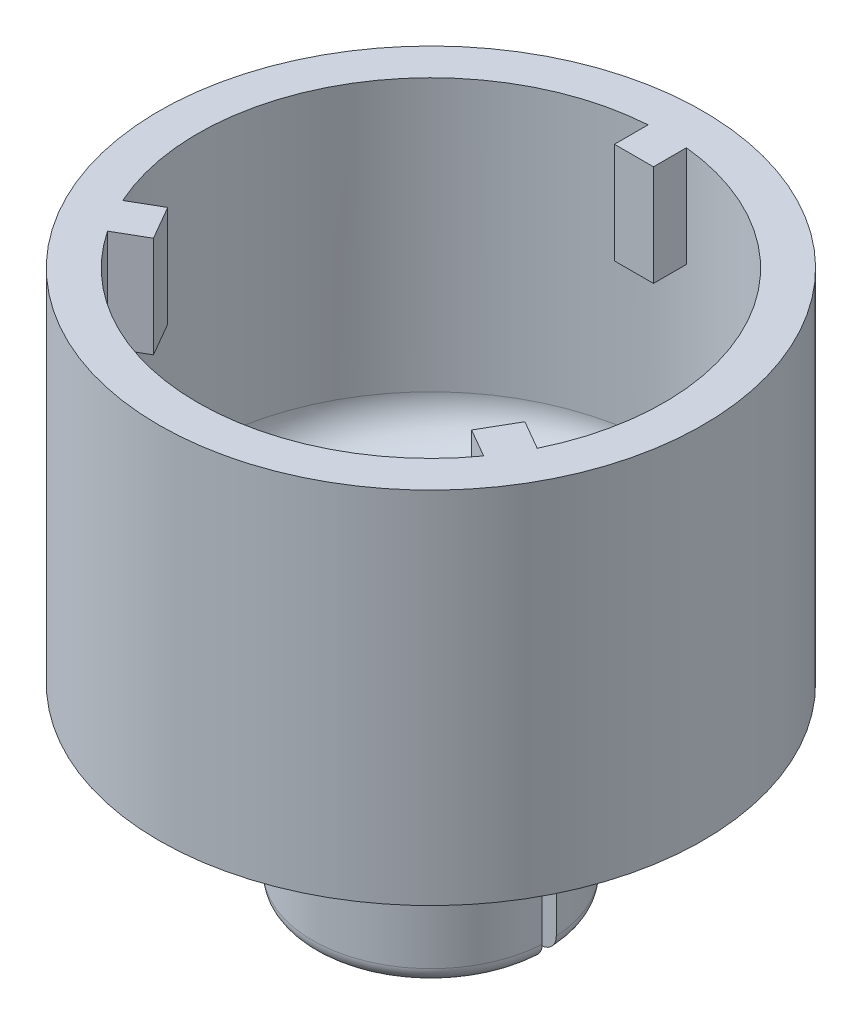
SolidWorks part; units mm, degrees
ref_plane "Front Plane" through (0, 0, 0) normal (0, 0, 1) x (1, 0, 0)
ref_plane "Top Plane" through (0, 0, 0) normal (0, 1, 0) x (1, 0, 0)
ref_plane "Right Plane" through (0, 0, 0) normal (1, 0, 0) x (0, 0, -1)
sketch "Sketch1" plane through (0, 0, 0) normal (0, 1, 0) x (1, 0, 0)
  circle A0 centre (0, 0) radius 35
  dimension "D1" = 70
extrude "Boss-Extrude1" add sketch "Sketch1" along normal blind 46.3
sketch "Sketch2" plane through (0, 46.3, 0) normal (0, 1, 0) x (1, 0, 0)
  circle A0 centre (0, 0) radius 30
  dimension "D1" = 60
extrude "Cut-Extrude1" cut sketch "Sketch2" against normal blind 40
sketch "Sketch3" plane through (0, 0, 0) normal (0, -1, 0) x (1, 0, 0)
  circle A0 centre (0, 0) radius 19.5
  dimension "D1" = 39
extrude "Boss-Extrude2" add sketch "Sketch3" along normal blind 7
sketch "Sketch4" plane through (0, -7, 0) normal (0, -1, 0) x (1, 0, 0)
  circle A0 centre (0, 0) radius 15.25
  dimension "D1" = 30.5
extrude "Boss-Extrude3" add sketch "Sketch4" along normal blind 16
fillet "Fillet1" radius 5 1 edges at (0, 0, -19.5)
sketch "Sketch5" plane through (0, 46.3, 0) normal (0, 1, 0) x (1, 0, 0)
  line L0 (-1.9905, 29.9339) -> (-1.9905, 25.6053)
  line L1 (-1.9905, 25.6053) -> (3.0302, 25.6053)
  line L2 (3.0302, 25.6053) -> (3.0302, 29.8466)
  line L3 (26.9188, -13.2431) -> (23.1701, -11.0788)
  line L4 (23.1701, -11.0788) -> (20.6597, -15.4269)
  line L5 (20.6597, -15.4269) -> (24.3328, -17.5475)
  line L6 (-24.9282, -16.6908) -> (-21.1796, -14.5265)
  line L7 (-21.1796, -14.5265) -> (-23.69, -10.1784)
  line L8 (-23.69, -10.1784) -> (-27.363, -12.299)
  circle A0 centre (0, 0) radius 30 construction
  arc A1 (24.3328, -17.5475) -> (26.9188, -13.2431) centre (0, 0) ccw
  circle A2 centre (0, 0) radius 30
  arc A3 (3.0302, 29.8466) -> (-1.9905, 29.9339) centre (0, 0) ccw
  arc A4 (-27.363, -12.299) -> (-24.9282, -16.6908) centre (0, 0) ccw
  point P19 (0, 0)
  dimension "D1" = 0
  dimension "D2" = 3
extrude "Boss-Extrude4" add sketch "Sketch5" against normal blind 13
sketch "Sketch7" plane through (0, -23, 0) normal (0, -1, 0) x (1, 0, 0)
  line L1 (33.0968, 0.9034) -> (-33.0968, 0.9034)
  line L2 (33.0968, 0.9034) -> (33.0968, -0.9034)
  line L3 (33.0968, -0.9034) -> (-33.0968, -0.9034)
  line L4 (-33.0968, 0.9034) -> (-33.0968, -0.9034)
  line L5 (33.0968, 0.9034) -> (-33.0968, -0.9034) construction
  line L6 (33.0968, -0.9034) -> (-33.0968, 0.9034) construction
  point P0 (0, 0)
extrude "Cut-Extrude2" cut sketch "Sketch7" against normal up to surface (16 mm away) up to face at (0, -7, -15.25)
fillet "Fillet2" radius 2 2 edges at (0, -23, 15.25) (0, -23, -15.25)
sketch "Sketch8" plane through (0, 6.3, 0) normal (0, 1, 0) x (1, 0, 0)
  circle A0 centre (0, 0) radius 10.3601
fillet "Fillet3" radius 5 1 edges at (0, 6.3, 30)
